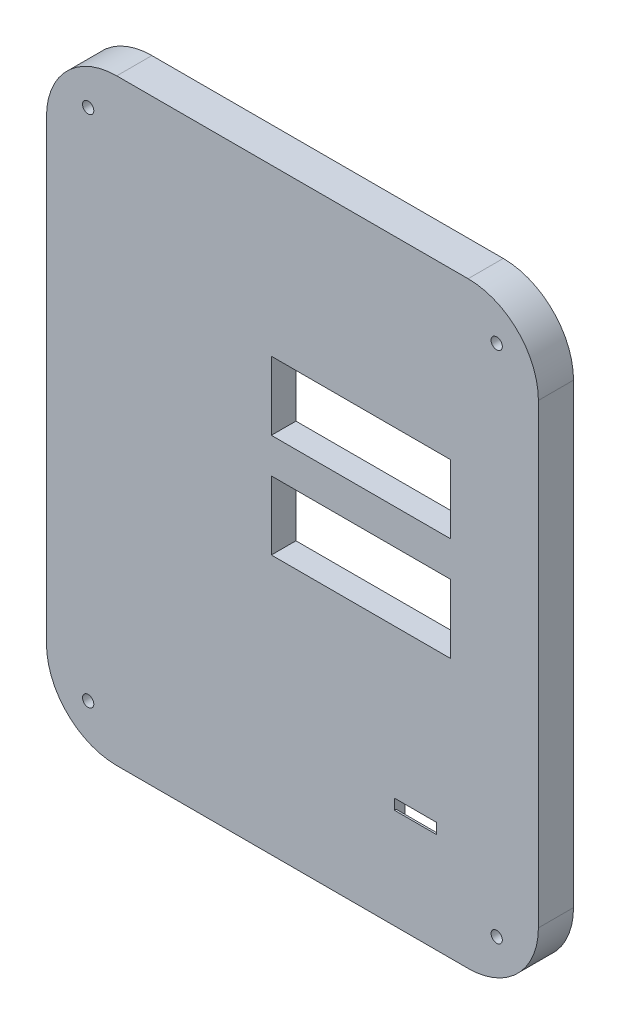
SolidWorks part; units mm, degrees
ref_plane "Front Plane" through (0, 0, 0) normal (0, 0, 1) x (1, 0, 0)
ref_plane "Top Plane" through (0, 0, 0) normal (0, 1, 0) x (1, 0, 0)
ref_plane "Right Plane" through (0, 0, 0) normal (1, 0, 0) x (0, 0, -1)
sketch "Sketch1" plane through (0, 0, 0) normal (0, 0, 1) x (1, 0, 0)
  line L0 (-57.5, 123) -> (42.5, 123) construction
  line L1 (62.5, 103) -> (62.5, -27) construction
  line L2 (-10.75, -47) -> (-57.5, -47) construction
  line L3 (-77.5, -27) -> (-77.5, 103) construction
  line L4 (-57.5, 123) -> (42.5, 123)
  line L5 (62.5, 103) -> (62.5, -27)
  line L6 (42.5, -47) -> (-57.5, -47)
  line L7 (-77.5, -27) -> (-77.5, 103)
  arc A0 (-57.5, 123) -> (-77.5, 103) centre (-57.5, 103) ccw construction
  arc A1 (62.5, 103) -> (42.5, 123) centre (42.5, 103) ccw construction
  arc A2 (42.5, -47) -> (62.5, -27) centre (42.5, -27) ccw construction
  arc A3 (-77.5, -27) -> (-57.5, -47) centre (-57.5, -27) ccw construction
  arc A4 (-57.5, 123) -> (-77.5, 103) centre (-57.5, 103) ccw
  arc A5 (62.5, 103) -> (42.5, 123) centre (42.5, 103) ccw
  arc A6 (42.5, -47) -> (62.5, -27) centre (42.5, -27) ccw
  arc A7 (-77.5, -27) -> (-57.5, -47) centre (-57.5, -27) ccw
extrude "Boss-Extrude1" add sketch "Sketch1" along normal blind 10
shell "Shell1" thickness 4 removed face at (-7.5, 38, 0)
ref_plane "Plane1" through (0, 38, 0) normal (0, 1, 0) x (1, 0, 0)
ref_plane "Plane2" through (-7.5, 0, 0) normal (1, 0, 0) x (0, 0, -1)
sketch "Sketch2" plane through (0, 0, 0) normal (0, 0, -1) x (-1, 0, 0)
  line L0 (58.2673, 117.1485) -> (61.4745, 109.409) construction
  line L1 (71.6485, 103.7673) -> (63.909, 106.9745) construction
  line L2 (58.2673, 117.1485) -> (61.4745, 109.409)
  line L3 (71.6485, 103.7673) -> (63.909, 106.9745)
  line L4 (-42.5, 119) -> (57.5, 119) construction
  line L5 (-42.5, 119) -> (57.5, 119)
  line L6 (73.5, 103) -> (73.5, -27) construction
  line L7 (73.5, 103) -> (73.5, -27)
  arc A0 (58.2673, 117.1485) -> (55.4958, 119) centre (55.4958, 116) ccw construction
  arc A1 (61.4745, 109.409) -> (63.909, 106.9745) centre (65.6317, 111.1317) ccw construction
  arc A2 (73.5, 100.9958) -> (71.6485, 103.7673) centre (70.5, 100.9958) ccw construction
  arc A3 (58.2673, 117.1485) -> (55.4958, 119) centre (55.4958, 116) ccw
  arc A4 (61.4745, 109.409) -> (63.909, 106.9745) centre (65.6317, 111.1317) ccw
  arc A5 (73.5, 100.9958) -> (71.6485, 103.7673) centre (70.5, 100.9958) ccw
  arc A6 (73.5, 103) -> (57.5, 119) centre (57.5, 103) ccw construction
  arc A7 (73.5, 103) -> (57.5, 119) centre (57.5, 103) ccw
  circle A8 centre (65.6317, 111.1317) radius 2.2 construction
  circle A9 centre (65.6317, 111.1317) radius 2.2 construction
  circle A10 centre (65.6317, 111.1317) radius 1.6
  arc M3 (57.5, 119) -> (73.5, 103) centre (57.5, 103) cw
  line M4 (73.5, 103) -> (73.5, -27)
  dimension "D1" = 3.2
extrude "Boss-Extrude2" add sketch "Sketch2" against normal up to surface (7 mm away) contours A5 L5 A3 L2 A4 L3 A10 M4 M3 | A10 region at (-57.3038, 118.7063, 0) region at (-65.6317, 111.1317, 0) up to face at (-7.5, 38, 7)
extrude "Cut-Extrude1" cut sketch "Sketch2<3>" against normal through all contours A10 region at (-65.6317, 111.1317, 0)
sketch "Sketch2<3>" plane through (0, 0, 0) normal (0, 0, -1) x (-1, 0, 0) same geometry as "Sketch2"
mirror "Mirror6" about plane through (0, 38, 0) normal (0, 1, 0) of "Cut-Extrude1", "Boss-Extrude2"
mirror "Mirror7" about plane through (-7.5, 0, 0) normal (1, 0, 0) of "Mirror6"
sketch "Sketch3" plane through (0, 0, 0) normal (0, 0, -1) x (-1, 0, 0)
  line L0 (73.5, 100.9958) -> (73.5, -24.9958) construction
  line L2 (71.6485, -27.7673) -> (63.909, -30.9745) construction
  line L6 (58.2673, -41.1485) -> (61.4745, -33.409) construction
  line L12 (55.4958, -43) -> (-40.4958, -43) construction
  line L20 (-43.2673, -41.1485) -> (-46.4745, -33.409) construction
  line L25 (-56.6485, -27.7673) -> (-48.909, -30.9745) construction
  line L26 (-58.5, -24.9958) -> (-58.5, 100.9958) construction
  line L27 (-56.6485, 103.7673) -> (-48.909, 106.9745) construction
  line L28 (-43.2673, 117.1485) -> (-46.4745, 109.409) construction
  line L29 (-40.4958, 119) -> (55.4958, 119) construction
  line L30 (58.2673, 117.1485) -> (61.4745, 109.409) construction
  line L31 (71.6485, 103.7673) -> (63.909, 106.9745) construction
  line L32 (55.4958, -43) -> (-40.4958, -43)
  line L33 (-43.2673, -41.1485) -> (-46.4745, -33.409)
  line L34 (-56.6485, -27.7673) -> (-48.909, -30.9745)
  line L35 (-58.5, -24.9958) -> (-58.5, 100.9958)
  line L36 (-56.6485, 103.7673) -> (-48.909, 106.9745)
  line L37 (-43.2673, 117.1485) -> (-46.4745, 109.409)
  line L38 (-40.4958, 119) -> (55.4958, 119)
  line L39 (58.2673, 117.1485) -> (61.4745, 109.409)
  line L40 (71.6485, 103.7673) -> (63.909, 106.9745)
  line L41 (73.5, 100.9958) -> (73.5, -24.9958)
  line L42 (71.6485, -27.7673) -> (63.909, -30.9745)
  line L43 (58.2673, -41.1485) -> (61.4745, -33.409)
  line L44 (55.4958, -42.5) -> (-40.4958, -42.5)
  line L45 (-42.8054, -40.9571) -> (-46.0126, -33.2176)
  line L46 (-56.4571, -27.3054) -> (-48.7176, -30.5126)
  line L47 (-58, -24.9958) -> (-58, 100.9958)
  line L48 (-56.4571, 103.3054) -> (-48.7176, 106.5126)
  line L49 (-42.8054, 116.9571) -> (-46.0126, 109.2176)
  line L50 (-40.4958, 118.5) -> (55.4958, 118.5)
  line L51 (57.8054, 116.9571) -> (61.0126, 109.2176)
  line L52 (71.4571, 103.3054) -> (63.7176, 106.5126)
  line L53 (73, 100.9958) -> (73, -24.9958)
  line L54 (71.4571, -27.3054) -> (63.7176, -30.5126)
  line L55 (57.8054, -40.9571) -> (61.0126, -33.2176)
  line L56 (55.4958, -40.5) -> (-40.4958, -40.5)
  line L57 (-40.9577, -40.1914) -> (-44.165, -32.4519)
  line L58 (-55.6914, -25.4577) -> (-47.9519, -28.665)
  line L59 (-56, -24.9958) -> (-56, 100.9958)
  line L60 (-55.6914, 101.4577) -> (-47.9519, 104.665)
  line L61 (-40.9577, 116.1914) -> (-44.165, 108.4519)
  line L62 (-40.4958, 116.5) -> (55.4958, 116.5)
  line L63 (55.9577, 116.1914) -> (59.165, 108.4519)
  line L64 (70.6914, 101.4577) -> (62.9519, 104.665)
  line L65 (71, 100.9958) -> (71, -24.9958)
  line L66 (70.6914, -25.4577) -> (62.9519, -28.665)
  line L67 (55.9577, -40.1914) -> (59.165, -32.4519)
  arc A0 (71.6485, -27.7673) -> (73.5, -24.9958) centre (70.5, -24.9958) ccw construction
  arc A2 (63.909, -30.9745) -> (61.4745, -33.409) centre (65.6317, -35.1317) ccw construction
  arc A6 (55.4958, -43) -> (58.2673, -41.1485) centre (55.4958, -40) ccw construction
  arc A12 (-43.2673, -41.1485) -> (-40.4958, -43) centre (-40.4958, -40) ccw construction
  arc A20 (-46.4745, -33.409) -> (-48.909, -30.9745) centre (-50.6317, -35.1317) ccw construction
  arc A21 (-58.5, -24.9958) -> (-56.6485, -27.7673) centre (-55.5, -24.9958) ccw construction
  arc A22 (-56.6485, 103.7673) -> (-58.5, 100.9958) centre (-55.5, 100.9958) ccw construction
  arc A23 (-48.909, 106.9745) -> (-46.4745, 109.409) centre (-50.6317, 111.1317) ccw construction
  arc A24 (-40.4958, 119) -> (-43.2673, 117.1485) centre (-40.4958, 116) ccw construction
  arc A25 (58.2673, 117.1485) -> (55.4958, 119) centre (55.4958, 116) ccw construction
  arc A26 (61.4745, 109.409) -> (63.909, 106.9745) centre (65.6317, 111.1317) ccw construction
  arc A27 (73.5, 100.9958) -> (71.6485, 103.7673) centre (70.5, 100.9958) ccw construction
  arc A28 (-43.2673, -41.1485) -> (-40.4958, -43) centre (-40.4958, -40) ccw
  arc A29 (-46.4745, -33.409) -> (-48.909, -30.9745) centre (-50.6317, -35.1317) ccw
  arc A30 (-58.5, -24.9958) -> (-56.6485, -27.7673) centre (-55.5, -24.9958) ccw
  arc A31 (-56.6485, 103.7673) -> (-58.5, 100.9958) centre (-55.5, 100.9958) ccw
  arc A32 (-48.909, 106.9745) -> (-46.4745, 109.409) centre (-50.6317, 111.1317) ccw
  arc A33 (-40.4958, 119) -> (-43.2673, 117.1485) centre (-40.4958, 116) ccw
  arc A34 (58.2673, 117.1485) -> (55.4958, 119) centre (55.4958, 116) ccw
  arc A35 (61.4745, 109.409) -> (63.909, 106.9745) centre (65.6317, 111.1317) ccw
  arc A36 (73.5, 100.9958) -> (71.6485, 103.7673) centre (70.5, 100.9958) ccw
  arc A37 (71.6485, -27.7673) -> (73.5, -24.9958) centre (70.5, -24.9958) ccw
  arc A38 (63.909, -30.9745) -> (61.4745, -33.409) centre (65.6317, -35.1317) ccw
  arc A39 (55.4958, -43) -> (58.2673, -41.1485) centre (55.4958, -40) ccw
  arc A40 (-42.8054, -40.9571) -> (-40.4958, -42.5) centre (-40.4958, -40) ccw
  arc A41 (-46.0126, -33.2176) -> (-48.7176, -30.5126) centre (-50.6317, -35.1317) ccw
  arc A42 (-58, -24.9958) -> (-56.4571, -27.3054) centre (-55.5, -24.9958) ccw
  arc A43 (-56.4571, 103.3054) -> (-58, 100.9958) centre (-55.5, 100.9958) ccw
  arc A44 (-48.7176, 106.5126) -> (-46.0126, 109.2176) centre (-50.6317, 111.1317) ccw
  arc A45 (-40.4958, 118.5) -> (-42.8054, 116.9571) centre (-40.4958, 116) ccw
  arc A46 (57.8054, 116.9571) -> (55.4958, 118.5) centre (55.4958, 116) ccw
  arc A47 (61.0126, 109.2176) -> (63.7176, 106.5126) centre (65.6317, 111.1317) ccw
  arc A48 (73, 100.9958) -> (71.4571, 103.3054) centre (70.5, 100.9958) ccw
  arc A49 (71.4571, -27.3054) -> (73, -24.9958) centre (70.5, -24.9958) ccw
  arc A50 (63.7176, -30.5126) -> (61.0126, -33.2176) centre (65.6317, -35.1317) ccw
  arc A51 (55.4958, -42.5) -> (57.8054, -40.9571) centre (55.4958, -40) ccw
  arc A52 (-40.9577, -40.1914) -> (-40.4958, -40.5) centre (-40.4958, -40) ccw
  arc A53 (-44.165, -32.4519) -> (-47.9519, -28.665) centre (-50.6317, -35.1317) ccw
  arc A54 (-56, -24.9958) -> (-55.6914, -25.4577) centre (-55.5, -24.9958) ccw
  arc A55 (-55.6914, 101.4577) -> (-56, 100.9958) centre (-55.5, 100.9958) ccw
  arc A56 (-47.9519, 104.665) -> (-44.165, 108.4519) centre (-50.6317, 111.1317) ccw
  arc A57 (-40.4958, 116.5) -> (-40.9577, 116.1914) centre (-40.4958, 116) ccw
  arc A58 (55.9577, 116.1914) -> (55.4958, 116.5) centre (55.4958, 116) ccw
  arc A59 (59.165, 108.4519) -> (62.9519, 104.665) centre (65.6317, 111.1317) ccw
  arc A60 (71, 100.9958) -> (70.6914, 101.4577) centre (70.5, 100.9958) ccw
  arc A61 (70.6914, -25.4577) -> (71, -24.9958) centre (70.5, -24.9958) ccw
  arc A62 (62.9519, -28.665) -> (59.165, -32.4519) centre (65.6317, -35.1317) ccw
  arc A63 (55.4958, -40.5) -> (55.9577, -40.1914) centre (55.4958, -40) ccw
  arc M4 (-43.2673, 117.1485) -> (-40.4958, 119) centre (-40.4958, 116) cw
  line M5 (-40.4958, 119) -> (55.4958, 119)
  arc M6 (55.4958, 119) -> (58.2673, 117.1485) centre (55.4958, 116) cw
  line M7 (58.2673, 117.1485) -> (61.4745, 109.409)
  arc M8 (61.4745, 109.409) -> (63.909, 106.9745) centre (65.6317, 111.1317) ccw
  line M9 (63.909, 106.9745) -> (71.6485, 103.7673)
  arc M10 (71.6485, 103.7673) -> (73.5, 100.9958) centre (70.5, 100.9958) cw
  line M11 (73.5, 100.9958) -> (73.5, -24.9958)
  arc M12 (73.5, -24.9958) -> (71.6485, -27.7673) centre (70.5, -24.9958) cw
  line M13 (71.6485, -27.7673) -> (63.909, -30.9745)
  arc M14 (63.909, -30.9745) -> (61.4745, -33.409) centre (65.6317, -35.1317) ccw
  line M15 (61.4745, -33.409) -> (58.2673, -41.1485)
  arc M16 (58.2673, -41.1485) -> (55.4958, -43) centre (55.4958, -40) cw
  line M17 (55.4958, -43) -> (-40.4958, -43)
  arc M18 (-40.4958, -43) -> (-43.2673, -41.1485) centre (-40.4958, -40) cw
  line M19 (-43.2673, -41.1485) -> (-46.4745, -33.409)
  arc M20 (-46.4745, -33.409) -> (-48.909, -30.9745) centre (-50.6317, -35.1317) ccw
  line M21 (-48.909, -30.9745) -> (-56.6485, -27.7673)
  arc M22 (-56.6485, -27.7673) -> (-58.5, -24.9958) centre (-55.5, -24.9958) cw
  line M23 (-58.5, -24.9958) -> (-58.5, 100.9958)
  arc M24 (-58.5, 100.9958) -> (-56.6485, 103.7673) centre (-55.5, 100.9958) cw
  line M25 (-56.6485, 103.7673) -> (-48.909, 106.9745)
  arc M26 (-48.909, 106.9745) -> (-46.4745, 109.409) centre (-50.6317, 111.1317) ccw
  line M27 (-46.4745, 109.409) -> (-43.2673, 117.1485)
  dimension "D1" = 0.5
  dimension "D2" = 2
extrude "Boss-Extrude3" add sketch "Sketch3" against normal up to surface (7 mm away) contours L44 A51 L55 A50 L54 A49 L53 A48 L52 A47 L51 A46 L50 A45 L49 A44 L48 A43 L47 A42 L46 A41 L45 A40 A63 L56 A52 L57 A53 L58 A54 L59 A55 L60 A56 L61 A57 L62 A58 L63 A59 L64 A60 L65 A61 L66 A62 L67 | A51 L44 A40 L45 A41 L46 A42 L47 A43 L48 A44 L49 A45 L50 A46 L51 A47 L52 A48 L53 A49 L54 A50 L55 M4 M27 M26 M25 M24 M23 M22 M21 M20 M19 M18 M17 M16 M15 M14 M13 M12 M11 M10 M9 M8 M7 M6 M5 region at (-7.5, -42.791, 0) region at (-7.5, -42.2924, 0) up to face at (-7.5, 38, 7)
extrude "Boss-Extrude4" add sketch "Sketch3<3>" along normal blind 2 contours L44 A51 L55 A50 L54 A49 L53 A48 L52 A47 L51 A46 L50 A45 L49 A44 L48 A43 L47 A42 L46 A41 L45 A40 A63 L56 A52 L57 A53 L58 A54 L59 A55 L60 A56 L61 A57 L62 A58 L63 A59 L64 A60 L65 A61 L66 A62 L67 region at (-7.5, -42.2924, 0)
sketch "Sketch3<3>" plane through (0, 0, 0) normal (0, 0, -1) x (-1, 0, 0) same geometry as "Sketch3"
sketch "Sketch4" plane through (0, 0, 7) normal (0, 0, -1) x (-1, 0, 0)
  line L0 (-12, 36.65) -> (-12, 66.15) construction
  line L1 (-37.5, 26.9) -> (13.5, 26.9)
  line L2 (-37.5, 26.9) -> (-37.5, 46.4)
  line L3 (-37.5, 46.4) -> (13.5, 46.4)
  line L4 (13.5, 26.9) -> (13.5, 46.4)
  line L5 (-37.5, 26.9) -> (13.5, 46.4) construction
  line L6 (-37.5, 46.4) -> (13.5, 26.9) construction
  line L7 (-37.5, 56.4) -> (13.5, 56.4)
  line L8 (-37.5, 56.4) -> (-37.5, 75.9)
  line L9 (-37.5, 75.9) -> (13.5, 75.9)
  line L10 (13.5, 56.4) -> (13.5, 75.9)
  line L11 (-37.5, 56.4) -> (13.5, 75.9) construction
  line L12 (-37.5, 75.9) -> (13.5, 56.4) construction
  line L13 (-14, 16.9) -> (72, 16.9) construction
  line L14 (-14, 16.9) -> (72, 16.9) construction
  line L15 (-62.5, -27) -> (-62.5, 103) construction
  point P0 (-12, 36.65)
  point P5 (-12, 66.15)
  dimension "D1" = 19.5
  dimension "D2" = 51
  dimension "D3" = 10
  dimension "D4" = 10
  dimension "D5" = 25
extrude "Cut-Extrude2" cut sketch "Sketch4" against normal through all
sketch "Sketch5" plane through (0, 0, 7) normal (0, 0, -1) x (-1, 0, 0)
  line L0 (13.5, 26.9) -> (13.5, 46.4) construction
  line L1 (13.5, 46.4) -> (-37.5, 46.4) construction
  line L2 (-37.5, 46.4) -> (-37.5, 26.9) construction
  line L3 (-37.5, 26.9) -> (13.5, 26.9) construction
  line L4 (13.5, 26.9) -> (13.5, 46.4)
  line L5 (13.5, 46.4) -> (-37.5, 46.4)
  line L6 (-37.5, 46.4) -> (-37.5, 26.9)
  line L7 (-37.5, 26.9) -> (13.5, 26.9)
  line L8 (18.4, 50.25) -> (-45.6, 50.25) construction
  line L9 (19.4, 24.05) -> (19.4, 49.25) construction
  line L10 (-45.6, 23.05) -> (18.4, 23.05) construction
  line L11 (-46.6, 49.25) -> (-46.6, 24.05) construction
  line L12 (18.4, 50.25) -> (-45.6, 50.25)
  line L13 (19.4, 24.05) -> (19.4, 49.25)
  line L14 (-45.6, 23.05) -> (18.4, 23.05)
  line L15 (-46.6, 49.25) -> (-46.6, 24.05)
  arc A0 (-45.6, 50.25) -> (-46.6, 49.25) centre (-45.6, 49.25) ccw construction
  arc A1 (19.4, 49.25) -> (18.4, 50.25) centre (18.4, 49.25) ccw construction
  arc A2 (18.4, 23.05) -> (19.4, 24.05) centre (18.4, 24.05) ccw construction
  arc A3 (-46.6, 24.05) -> (-45.6, 23.05) centre (-45.6, 24.05) ccw construction
  arc A4 (-45.6, 50.25) -> (-46.6, 49.25) centre (-45.6, 49.25) ccw
  arc A5 (19.4, 49.25) -> (18.4, 50.25) centre (18.4, 49.25) ccw
  arc A6 (18.4, 23.05) -> (19.4, 24.05) centre (18.4, 24.05) ccw
  arc A7 (-46.6, 24.05) -> (-45.6, 23.05) centre (-45.6, 24.05) ccw
  arc A8 (14.952, 46.6089) -> (17.848, 48.1911) centre (16.4, 47.4) ccw construction
  arc A9 (14.952, 46.6089) -> (17.848, 48.1911) centre (16.4, 47.4) ccw construction
  arc A10 (17.848, 48.1911) -> (14.952, 46.6089) centre (16.4, 47.4) ccw construction
  arc A11 (17.848, 48.1911) -> (14.952, 46.6089) centre (16.4, 47.4) ccw construction
  arc A12 (14.952, 25.1089) -> (17.848, 26.6911) centre (16.4, 25.9) ccw construction
  arc A13 (17.848, 26.6911) -> (14.952, 25.1089) centre (16.4, 25.9) ccw construction
  arc A14 (14.952, 25.1089) -> (17.848, 26.6911) centre (16.4, 25.9) ccw construction
  arc A15 (17.848, 26.6911) -> (14.952, 25.1089) centre (16.4, 25.9) ccw construction
  arc A16 (-42.152, 26.6911) -> (-45.048, 25.1089) centre (-43.6, 25.9) ccw construction
  arc A17 (-45.048, 25.1089) -> (-42.152, 26.6911) centre (-43.6, 25.9) ccw construction
  arc A18 (-42.152, 26.6911) -> (-45.048, 25.1089) centre (-43.6, 25.9) ccw construction
  arc A19 (-45.048, 25.1089) -> (-42.152, 26.6911) centre (-43.6, 25.9) ccw construction
  arc A20 (-42.152, 48.1911) -> (-45.048, 46.6089) centre (-43.6, 47.4) ccw construction
  arc A21 (-45.048, 46.6089) -> (-42.152, 48.1911) centre (-43.6, 47.4) ccw construction
  arc A22 (-42.152, 48.1911) -> (-45.048, 46.6089) centre (-43.6, 47.4) ccw construction
  arc A23 (-45.048, 46.6089) -> (-42.152, 48.1911) centre (-43.6, 47.4) ccw construction
  circle A24 centre (16.4, 47.4) radius 2.2
  circle A25 centre (16.4, 25.9) radius 2.2
  circle A26 centre (-43.6, 47.4) radius 2.2
  circle A27 centre (-43.6, 25.9) radius 2.2
  line M17 (-37.5, 46.4) -> (13.5, 46.4)
  line M18 (13.5, 46.4) -> (13.5, 26.9)
  line M19 (13.5, 26.9) -> (-37.5, 26.9)
  line M20 (-37.5, 26.9) -> (-37.5, 46.4)
  dimension "D1" = 4.4
extrude "Boss-Extrude5" add sketch "Sketch5" along normal blind 4 contours L15 A7 L14 A6 L13 A5 L12 A4 A27 A26 A25 A24 M20 M17 M18 M19 | A25 | A24 | A26 | A27 region at (-18.6023, 49.4523, 7) region at (-16.4, 47.4, 7) region at (-16.4, 25.9, 7) region at (43.6, 47.4, 7) region at (43.6, 25.9, 7)
sketch "Sketch6" plane through (0, 0, 3) normal (0, 0, -1) x (-1, 0, 0)
  line L0 (-41.77, 30.96) -> (-39.03, 30.96) construction
  line L1 (-41.77, 41.32) -> (-41.77, 30.96) construction
  line L2 (-39.03, 41.32) -> (-41.77, 41.32) construction
  line L3 (-39.03, 30.96) -> (-39.03, 41.32) construction
  line L4 (-39.03, 41.32) -> (-41.77, 41.32)
  line L5 (-39.03, 30.96) -> (-39.03, 41.32)
  line L6 (-41.77, 30.96) -> (-39.03, 30.96)
  line L7 (-41.77, 41.32) -> (-41.77, 30.96)
  line L8 (17.77, 41.32) -> (15.03, 41.32) construction
  line L9 (15.03, 41.32) -> (15.03, 30.96) construction
  line L10 (15.03, 30.96) -> (17.77, 30.96) construction
  line L11 (17.77, 30.96) -> (17.77, 41.32) construction
  line L12 (17.77, 41.32) -> (15.03, 41.32)
  line L13 (15.03, 41.32) -> (15.03, 30.96)
  line L14 (15.03, 30.96) -> (17.77, 30.96)
  line L15 (17.77, 30.96) -> (17.77, 41.32)
extrude "Cut-Extrude3" cut sketch "Sketch6" against normal blind 3
extrude "Cut-Extrude4" cut sketch "Sketch5<3>" against normal blind 4.5 from surface contours A25 | A24 | A26 | A27 region at (-16.4, 47.4, 7) region at (-16.4, 25.9, 7) region at (43.6, 47.4, 7) region at (43.6, 25.9, 7) starting at face at (40.4, 36.14, 3)
sketch "Sketch5<3>" plane through (0, 0, 7) normal (0, 0, -1) x (-1, 0, 0) same geometry as "Sketch5"
chamfer "Chamfer1" distance 0.5 angle 45 4 edges at (-18.6, 47.4, 3) (-18.6, 25.9, 3) (41.4, 25.9, 3) (41.4, 47.4, 3)
pattern_sketch "Sketch-Pattern1" of "Chamfer1", "Cut-Extrude4", "Cut-Extrude3", "Boss-Extrude5" driven by "Sketch4"
sketch "Sketch7" plane through (0, 0, 7) normal (0, 0, -1) x (-1, 0, 0)
  line L0 (-62.5, -27) -> (-62.5, 103) construction
  line L1 (-21.5, -15.5) -> (-33.5, -15.5)
  line L2 (-21.5, -15.5) -> (-21.5, -30.5)
  line L3 (-21.5, -30.5) -> (-33.5, -30.5)
  line L4 (-33.5, -15.5) -> (-33.5, -30.5)
  line L5 (-21.5, -15.5) -> (-33.5, -30.5) construction
  line L6 (-21.5, -30.5) -> (-33.5, -15.5) construction
  line L7 (57.5, -47) -> (-42.5, -47) construction
  line L9 (-33.5, -15.5) -> (-21.5, -15.5)
  line L10 (-33.5, -15.5) -> (-33.5, -18.5)
  line L11 (-33.5, -18.5) -> (-21.5, -18.5)
  line L12 (-21.5, -15.5) -> (-21.5, -18.5)
  point P0 (-27.5, -23)
  dimension "D1" = 35
  dimension "D2" = 24
  dimension "D3" = 15
  dimension "D4" = 12
  dimension "D5" = 3
extrude "Cut-Extrude5" cut sketch "Sketch7" against normal offset from surface (2.5 mm away) 0.5 contours L11 L4 L3 L2 region at (27.5, -24.5, 7) up to face at (12, 36.65, 10)
extrude "Cut-Extrude6" cut sketch "Sketch7<3>" against normal through all contours L4 L11 L2 L1 region at (27.5, -17, 7)
sketch "Sketch7<3>" plane through (0, 0, 7) normal (0, 0, -1) x (-1, 0, 0) same geometry as "Sketch7"
